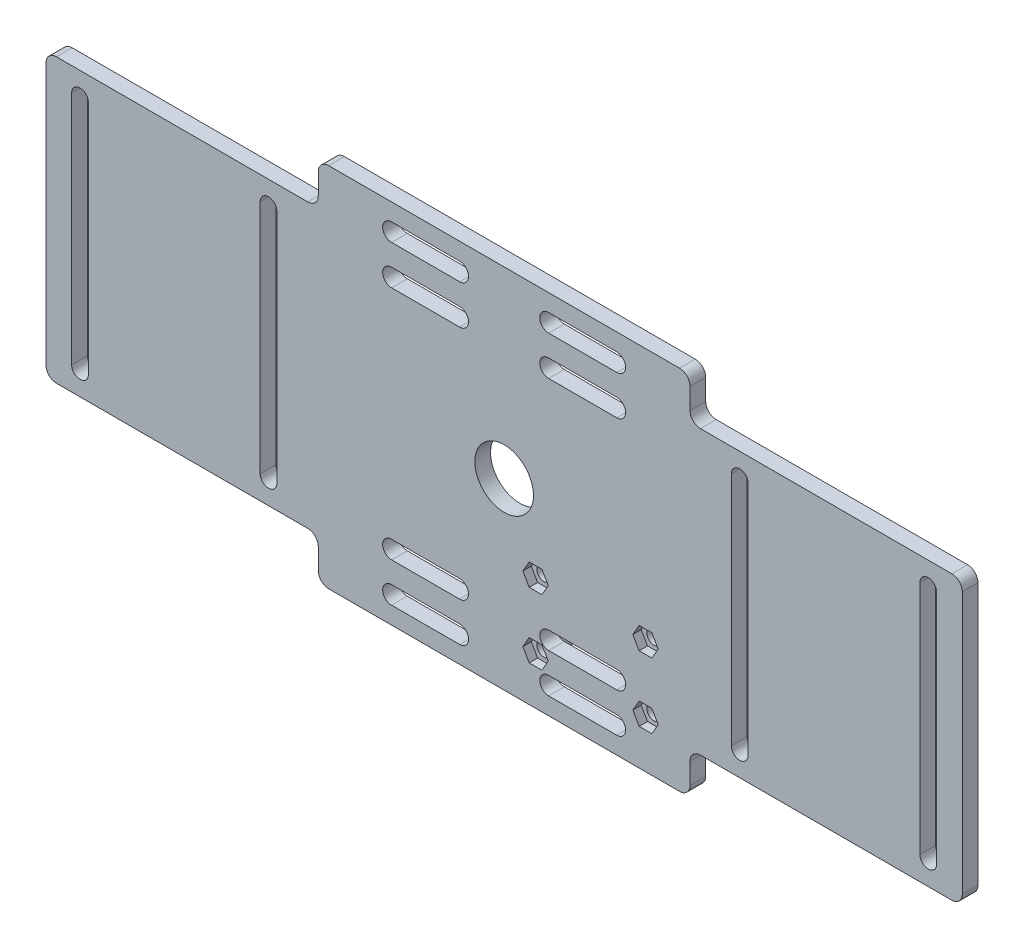
SolidWorks part; units mm, degrees
ref_plane "前基準面" through (0, 0, 0) normal (0, 0, 1) x (1, 0, 0)
ref_plane "上基準面" through (0, 0, 0) normal (0, 1, 0) x (1, 0, 0)
ref_plane "右基準面" through (0, 0, 0) normal (1, 0, 0) x (0, 0, -1)
sketch "草圖1" plane through (0, 0, 0) normal (0, 0, 1) x (1, 0, 0)
  line L0 (35.5, 33) -> (35.5, 29)
  line L1 (-33.5, 35) -> (33.5, 35)
  line L2 (-87.5, 25) -> (-87.5, -25)
  line L3 (-33.5, -35) -> (33.5, -35)
  line L4 (87.5, 25) -> (87.5, -25)
  line L5 (-87.5, 35) -> (87.5, -35) construction
  line L6 (-87.5, -35) -> (87.5, 35) construction
  line L7 (37.5, 27) -> (85.5, 27)
  line L8 (0, 71.4811) -> (0, -70.0061) construction
  line L9 (-113.0104, 0) -> (128.372, 0) construction
  line L10 (-37.5, 27) -> (-85.5, 27)
  line L11 (-35.5, 33) -> (-35.5, 29)
  line L12 (37.5, -27) -> (85.5, -27)
  line L13 (35.5, -33) -> (35.5, -29)
  line L14 (-35.5, -33) -> (-35.5, -29)
  line L15 (-37.5, -27) -> (-85.5, -27)
  arc A0 (35.5, 33) -> (33.5, 35) centre (33.5, 33) ccw
  arc A1 (37.5, 27) -> (35.5, 29) centre (37.5, 29) cw
  arc A2 (87.5, 25) -> (85.5, 27) centre (85.5, 25) ccw
  arc A3 (-87.5, 25) -> (-85.5, 27) centre (-85.5, 25) cw
  arc A4 (-37.5, 27) -> (-35.5, 29) centre (-37.5, 29) ccw
  arc A5 (-35.5, 33) -> (-33.5, 35) centre (-33.5, 33) cw
  arc A6 (87.5, -25) -> (85.5, -27) centre (85.5, -25) cw
  arc A7 (37.5, -27) -> (35.5, -29) centre (37.5, -29) ccw
  arc A8 (35.5, -33) -> (33.5, -35) centre (33.5, -33) cw
  arc A9 (-35.5, -33) -> (-33.5, -35) centre (-33.5, -33) ccw
  arc A10 (-37.5, -27) -> (-35.5, -29) centre (-37.5, -29) cw
  arc A11 (-87.5, -25) -> (-85.5, -27) centre (-85.5, -25) ccw
  point P0 (0, 0)
  point P13 (35.5, 27)
  point P29 (-35.5, 27)
  point P39 (35.5, -27)
  point P49 (-35.5, -27)
  dimension "D1" = 2
  dimension "D2" = 2
  dimension "D3" = 2
  dimension "D4" = 175
  dimension "D5" = 70
  dimension "D6" = 8
  dimension "D7" = 52
extrude "填料-伸長1" add sketch "草圖1" along normal blind 3
sketch "草圖2" plane through (0, 0, 3) normal (0, 0, 1) x (1, 0, 0)
  line L0 (-1000, 0) -> (49000, 0) construction
  line L1 (45, -986.1952) -> (45, 49013.8048) construction
  line L2 (-81, -962.7943) -> (-81, 49037.2057) construction
  line L3 (45, -22.5) -> (45, 22.5) construction
  line L4 (43.4, -22.5) -> (43.4, 22.5)
  line L5 (46.6, -22.5) -> (46.6, 22.5)
  line L6 (-45, -1000) -> (-45, 49000) construction
  line L7 (-45, -22.5) -> (-45, 22.5) construction
  line L8 (-46.6, -22.5) -> (-46.6, 22.5)
  line L9 (-43.4, -22.5) -> (-43.4, 22.5)
  line L10 (0, -1000) -> (0, 49000) construction
  line L11 (-1010.5287, 30) -> (48989.4713, 30) construction
  line L12 (-1007.193, -30) -> (48992.807, -30) construction
  line L13 (21.5, -30) -> (8.5, -30) construction
  line L16 (6, -996.0597) -> (6, 49003.9403) construction
  line L19 (81, -968.4295) -> (81, 49031.5705) construction
  line L20 (-81, -22.5) -> (-81, 22.5) construction
  line L21 (-82.6, -22.5) -> (-82.6, 22.5)
  line L22 (-79.4, -22.5) -> (-79.4, 22.5)
  line L23 (81, -22.5) -> (81, 22.5) construction
  line L24 (79.4, -22.5) -> (79.4, 22.5)
  line L25 (82.6, -22.5) -> (82.6, 22.5)
  line L26 (27, -997.4467) -> (27, 49002.5533) construction
  line L27 (-1014.4971, -26) -> (48985.5029, -26) construction
  line L28 (-1015.8254, -13.5) -> (48984.1746, -13.5) construction
  line L29 (-33.5, -35) -> (33.5, -35) construction
  line L30 (21.5, -31.7) -> (8.5, -31.7)
  line L33 (21.5, -28.3) -> (8.5, -28.3)
  line L34 (-21.5, -30) -> (-8.5, -30) construction
  line L35 (-21.5, -31.7) -> (-8.5, -31.7)
  line L36 (-21.5, -28.3) -> (-8.5, -28.3)
  line L37 (21.5, 30) -> (8.5, 30) construction
  line L38 (21.5, 31.7) -> (8.5, 31.7)
  line L39 (21.5, 28.3) -> (8.5, 28.3)
  line L40 (-21.5, 30) -> (-8.5, 30) construction
  line L41 (-21.5, 31.7) -> (-8.5, 31.7)
  line L42 (-21.5, 28.3) -> (-8.5, 28.3)
  line L43 (21.5, 22.5) -> (8.5, 22.5) construction
  line L44 (21.5, 24.2) -> (8.5, 24.2)
  line L45 (21.5, 20.8) -> (8.5, 20.8)
  line L46 (-21.5, 22.5) -> (-8.5, 22.5) construction
  line L47 (-21.5, 24.2) -> (-8.5, 24.2)
  line L48 (-21.5, 20.8) -> (-8.5, 20.8)
  line L49 (-21.5, -22.5) -> (-8.5, -22.5) construction
  line L50 (-21.5, -24.2) -> (-8.5, -24.2)
  line L51 (-21.5, -20.8) -> (-8.5, -20.8)
  line L52 (21.5, -22.5) -> (8.5, -22.5) construction
  line L53 (21.5, -24.2) -> (8.5, -24.2)
  line L54 (21.5, -20.8) -> (8.5, -20.8)
  arc A0 (43.4, -22.5) -> (46.6, -22.5) centre (45, -22.5) ccw
  arc A1 (46.6, 22.5) -> (43.4, 22.5) centre (45, 22.5) ccw
  arc A2 (-46.6, -22.5) -> (-43.4, -22.5) centre (-45, -22.5) ccw
  arc A3 (-43.4, 22.5) -> (-46.6, 22.5) centre (-45, 22.5) ccw
  arc A12 (-82.6, -22.5) -> (-79.4, -22.5) centre (-81, -22.5) ccw
  arc A13 (-79.4, 22.5) -> (-82.6, 22.5) centre (-81, 22.5) ccw
  arc A14 (79.4, -22.5) -> (82.6, -22.5) centre (81, -22.5) ccw
  arc A15 (82.6, 22.5) -> (79.4, 22.5) centre (81, 22.5) ccw
  circle A16 centre (0, 0) radius 5.6
  circle A17 centre (27, -13.5) radius 1.35
  circle A18 centre (6, -13.5) radius 1.35
  circle A19 centre (6, -26) radius 1.35
  circle A20 centre (27, -26) radius 1.35
  arc A23 (21.5, -31.7) -> (21.5, -28.3) centre (21.5, -30) ccw
  arc A24 (8.5, -28.3) -> (8.5, -31.7) centre (8.5, -30) ccw
  arc A25 (-21.5, -31.7) -> (-21.5, -28.3) centre (-21.5, -30) cw
  arc A26 (-8.5, -28.3) -> (-8.5, -31.7) centre (-8.5, -30) cw
  arc A27 (21.5, 31.7) -> (21.5, 28.3) centre (21.5, 30) cw
  arc A28 (8.5, 28.3) -> (8.5, 31.7) centre (8.5, 30) cw
  arc A29 (-21.5, 31.7) -> (-21.5, 28.3) centre (-21.5, 30) ccw
  arc A30 (-8.5, 28.3) -> (-8.5, 31.7) centre (-8.5, 30) ccw
  arc A31 (21.5, 24.2) -> (21.5, 20.8) centre (21.5, 22.5) cw
  arc A32 (8.5, 20.8) -> (8.5, 24.2) centre (8.5, 22.5) cw
  arc A33 (-21.5, 24.2) -> (-21.5, 20.8) centre (-21.5, 22.5) ccw
  arc A34 (-8.5, 20.8) -> (-8.5, 24.2) centre (-8.5, 22.5) ccw
  arc A35 (-21.5, -24.2) -> (-21.5, -20.8) centre (-21.5, -22.5) cw
  arc A36 (-8.5, -20.8) -> (-8.5, -24.2) centre (-8.5, -22.5) cw
  arc A37 (21.5, -24.2) -> (21.5, -20.8) centre (21.5, -22.5) ccw
  arc A38 (8.5, -20.8) -> (8.5, -24.2) centre (8.5, -22.5) ccw
  point P9 (45, 0)
  point P16 (-45, 0)
  point P31 (15, -30)
  point P47 (-81, 0)
  point P54 (81, 0)
  point P72 (-15, -30)
  point P81 (15, 30)
  point P88 (-15, 30)
  point P97 (15, 22.5)
  point P102 (-15, 22.5)
  point P110 (-15, -22.5)
  point P116 (15, -22.5)
  dimension "D10" = 1.7
  dimension "D20" = 11.2
  dimension "D21" = 2.7
  dimension "D27" = 7.5
  dimension "D2" = 45
  dimension "D3" = 3.2
  dimension "D4" = 90
  dimension "D5" = 45
  dimension "D6" = 3.2
  dimension "D7" = 45
  dimension "D8" = 60
  dimension "D9" = 30
  dimension "D11" = 13
  dimension "D12" = 12.5
  dimension "D13" = 21
  dimension "D14" = 162
  dimension "D15" = 81
  dimension "D16" = 3.2
  dimension "D17" = 45
  dimension "D18" = 45
  dimension "D19" = 3.2
  dimension "D22" = 9
  dimension "D23" = 6
  dimension "D24" = 8.5
  dimension "D25" = 2
  dimension "D28" = 7.5
  dimension "D26" = 2
extrude "除料-伸長1" cut sketch "草圖2" against normal through all
sketch "草圖3" plane through (0, 0, 3) normal (0, 0, 1) x (1, 0, 0)
  line L0 (29.4249, -26) -> (28.2124, -23.9)
  line L1 (8.4249, -26) -> (7.2124, -23.9)
  line L2 (7.2124, -23.9) -> (4.7876, -23.9)
  line L3 (4.7876, -23.9) -> (3.5751, -26)
  line L4 (3.5751, -26) -> (4.7876, -28.1)
  line L5 (4.7876, -28.1) -> (7.2124, -28.1)
  line L6 (7.2124, -28.1) -> (8.4249, -26)
  line L7 (28.2124, -23.9) -> (25.7876, -23.9)
  line L8 (25.7876, -23.9) -> (24.5751, -26)
  line L9 (24.5751, -26) -> (25.7876, -28.1)
  line L10 (25.7876, -28.1) -> (28.2124, -28.1)
  line L11 (28.2124, -28.1) -> (29.4249, -26)
  line L12 (29.4249, -13.5) -> (28.2124, -11.4)
  line L13 (28.2124, -11.4) -> (25.7876, -11.4)
  line L14 (25.7876, -11.4) -> (24.5751, -13.5)
  line L15 (24.5751, -13.5) -> (25.7876, -15.6)
  line L16 (25.7876, -15.6) -> (28.2124, -15.6)
  line L17 (28.2124, -15.6) -> (29.4249, -13.5)
  line L18 (8.4249, -13.5) -> (7.2124, -11.4)
  line L19 (7.2124, -11.4) -> (4.7876, -11.4)
  line L20 (4.7876, -11.4) -> (3.5751, -13.5)
  line L21 (3.5751, -13.5) -> (4.7876, -15.6)
  line L22 (4.7876, -15.6) -> (7.2124, -15.6)
  line L23 (7.2124, -15.6) -> (8.4249, -13.5)
  circle A0 centre (6, -26) radius 2.1 construction
  circle A3 centre (27, -26) radius 2.1 construction
  circle A4 centre (27, -13.5) radius 2.1 construction
  circle A5 centre (6, -13.5) radius 2.1 construction
  dimension "D1" = 4.2
  dimension "D2" = 2
  dimension "D3" = 2
extrude "除料-伸長2" cut sketch "草圖3" against normal blind 1.6
sketch "草圖4" plane through (0, 0, 0) normal (0, 0, -1) x (-1, 0, 0)
  circle A0 centre (-27, -13.5) radius 1.35
  circle A1 centre (-27, -26) radius 1.25
  circle A2 centre (-6, -13.5) radius 1.25
  circle A3 centre (-6, -26) radius 1.25
  circle A4 centre (-27, -13.5) radius 2.1
  circle A5 centre (-27, -26) radius 2
  circle A6 centre (-6, -13.5) radius 2
  circle A7 centre (-6, -26) radius 2
  circle A8 centre (-27, -13.5) radius 1.35 construction
  dimension "D1" = 0.75
extrude "填料-伸長2" add sketch "草圖4" along normal blind 2
chamfer "導角1" distance 0.5 angle 30 4 edges at (25.65, -13.5, -2) (4.75, -13.5, -2) (4.75, -26, -2) (25.75, -26, -2) first distance on face at (24.9, -13.5, -2) first distance on face at (4, -13.5, -2) first distance on face at (4, -26, -2) first distance on face at (25, -26, -2)
fillet "圓角2" radius 0.5 4 edges at (29.1, -13.5, 0) (8, -13.5, 0) (8, -26, 0) (29, -26, 0)
